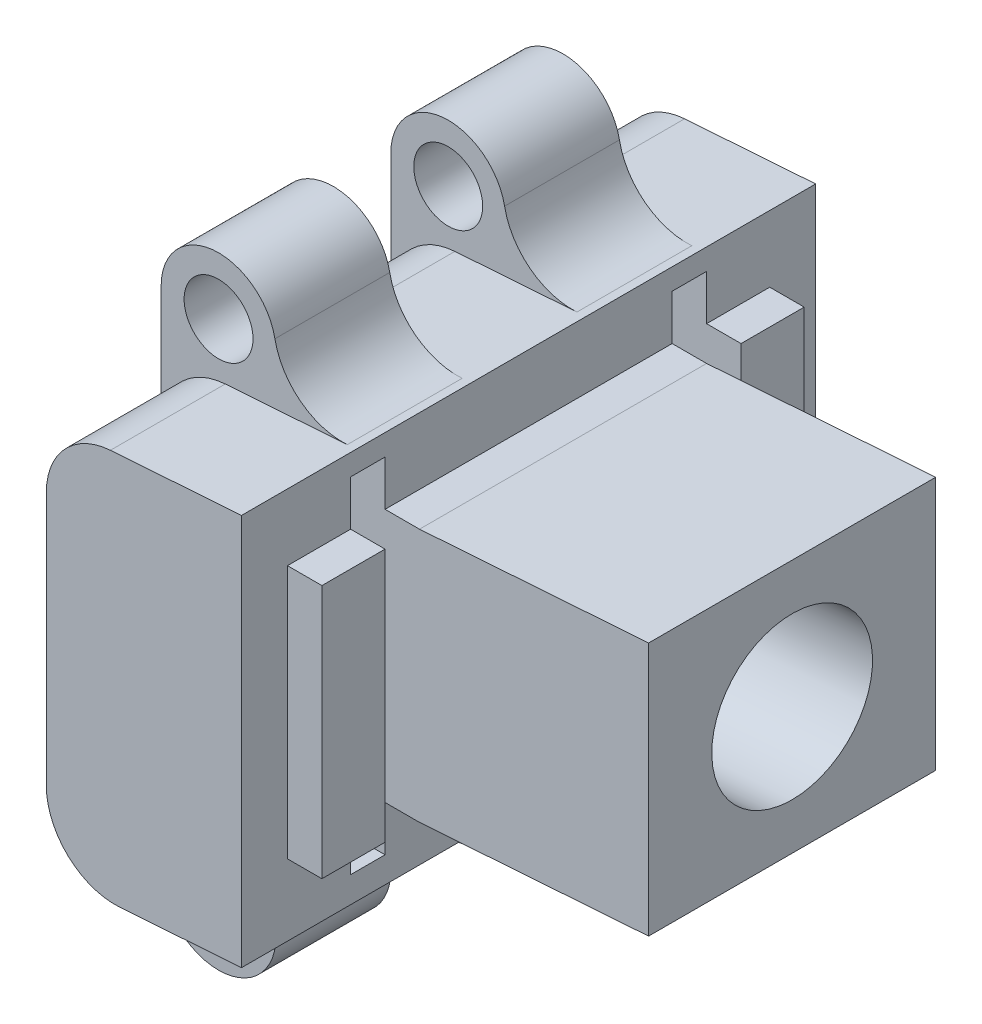
SolidWorks part; units mm, degrees
ref_plane "Front Plane" through (0, 0, 0) normal (0, 0, 1) x (1, 0, 0)
ref_plane "Top Plane" through (0, 0, 0) normal (0, 1, 0) x (1, 0, 0)
ref_plane "Right Plane" through (0, 0, 0) normal (1, 0, 0) x (0, 0, -1)
sketch "Sketch1" plane through (0, 0, 0) normal (1, 0, 0) x (0, 0, -1)
  line L1 (0, 0) -> (50, 0)
  line L2 (0, 0) -> (0, 34.11)
  line L3 (0, 34.11) -> (50, 34.11)
  line L4 (50, 0) -> (50, 34.11)
  dimension "D1" = 50
  dimension "D2" = 34.11
extrude "Boss-Extrude1" add sketch "Sketch1" along normal blind 20
sketch "Sketch2" plane through (0, 0, 0) normal (0, 0, 1) x (1, 0, 0)
  line L0 (3, 37.11) -> (3, 34.11) construction
  line L1 (20, 34.11) -> (0, 34.11) construction
  line L2 (0, 34.11) -> (0, 37.11)
  line L3 (0, 34.11) -> (3, 34.11)
  line L4 (3, 34.11) -> (6, 34.11)
  line L5 (6, 34.11) -> (6, 37.11)
  line L6 (6, 37.11) -> (3, 37.11) construction
  circle A0 centre (3, 37.11) radius 2
  arc A1 (6, 37.11) -> (0, 37.11) centre (3, 37.11) ccw
  dimension "D1" = 4
  dimension "D2" = 3
  dimension "D3" = 3
ref_plane "Plane1" through (0, 0, -10) normal (0, 0, 1) x (1, 0, 0)
sketch "Sketch3" plane through (0, 0, -10) normal (0, 0, 1) x (1, 0, 0)
  line L0 (5, 39.11) -> (5, 34.11) construction
  line L2 (0, 34.11) -> (0, 39.11)
  line L3 (0, 34.11) -> (5, 34.11)
  line L4 (5, 34.11) -> (10, 34.11)
  line L5 (10, 34.11) -> (10, 39.11)
  line L6 (10, 39.11) -> (5, 39.11) construction
  line L7 (0, 34.11) -> (0, 0) construction
  line L8 (20, 34.11) -> (0, 34.11) construction
  circle A0 centre (5, 39.11) radius 3
  arc A1 (10, 39.11) -> (0, 39.11) centre (5, 39.11) ccw
  dimension "D1" = 6
  dimension "D2" = 5
  dimension "D3" = 5
extrude "Boss-Extrude2" add sketch "Sketch3" against normal blind 10
pattern_linear "LPattern1" count 2 spacing 20 along (0, 0, -1) of "Boss-Extrude2"
ref_plane "Plane2" through (0, 17.055, 0) normal (0, 1, 0) x (1, 0, 0)
mirror "Mirror1" about plane through (0, 17.055, 0) normal (0, 1, 0) of "LPattern1", "Boss-Extrude2"
ref_plane "Plane3" through (0, 0, -25) normal (0, 0, 1) x (1, 0, 0)
sketch "Sketch4" plane through (0, 0, -25) normal (0, 0, 1) x (1, 0, 0)
  line L0 (20, 17.055) -> (0, 17.055) construction
  line L1 (20, 34.11) -> (20, 0) construction
  line L2 (0, 34.11) -> (0, 0) construction
  line L3 (10, 0) -> (10, 34.11) construction
  line L4 (20, 0) -> (0, 0) construction
  line L5 (20, 34.11) -> (0, 34.11) construction
  line L6 (10, 17.055) -> (20, 17.7543) construction
  dimension "D1" = 4
ref_plane "Plane4" through (20, 17.7543, -25) normal (0.9976, 0.0698, 0) x (0, 0, -1)
sketch "Sketch7" plane through (0, 0, 0) normal (0, 0, 1) x (1, 0, 0)
  line L0 (20, 34.11) -> (0, 34.11)
  line L1 (0, 34.11) -> (20, 35.5085)
  line L2 (20, 35.5085) -> (20, 34.11)
  dimension "D1" = 4
extrude "Boss-Extrude3" add sketch "Sketch7" against normal up to surface (50 mm away) up to face at (10, 17.055, -50)
sketch "Sketch8" plane through (0, 0, 0) normal (0, 0, 1) x (1, 0, 0)
  line L0 (0, 0) -> (20, 1.3985)
  line L1 (20, 35.5085) -> (20, 0) construction
  line L2 (20, 1.3985) -> (20, 0)
  line L3 (20, 0) -> (0, 0)
  dimension "D1" = 4
extrude "Cut-Extrude3" cut sketch "Sketch8" against normal blind 10
extrude "Cut-Extrude4" cut sketch "Sketch8<2>" against normal up to surface (30 mm away) from surface up to face at (5, -3.75, -30) starting at face at (5, -3.75, -20)
sketch "Sketch8<2>" plane through (0, 0, 0) normal (0, 0, 1) x (1, 0, 0) same geometry as "Sketch8"
extrude "Cut-Extrude5" cut sketch "Sketch8<3>" along direction (0, 0, 1) on the side against the normal up to surface (50 mm away) from surface up to face at (10, 17.4046, -50) starting at face at (5, -3.75, -40)
sketch "Sketch8<3>" plane through (0, 0, 0) normal (0, 0, 1) x (1, 0, 0) same geometry as "Sketch8"
sketch "Sketch9" plane through (0, 0, 0) normal (0, 0, 1) x (1, 0, 0)
  line L0 (20, 1.3985) -> (0, 0) construction
  line L1 (20, 0) -> (20, 1.3985) construction
  line L2 (10, 0) -> (20, 0) construction
  line L3 (20, 1.3985) -> (10, 0.6993)
  line L4 (20, 0) -> (20, 1.3985)
  line L5 (10, 0) -> (20, 0)
  line L6 (10, 0) -> (10, 0.6993)
extrude "Cut-Extrude6" cut sketch "Sketch9" against normal up to surface (50 mm away) up to face at (10, 17.7543, -50)
sketch "Sketch6" plane through (20, 0, 0) normal (1, 0, 0) x (0, 0, -1)
  line L0 (25, 35.5085) -> (25, 18.4535) construction
  line L3 (12.5, 18.4535) -> (37.5, 18.4535)
  line L4 (12.5, 3.4535) -> (12.5, 33.4535)
  line L5 (12.5, 33.4535) -> (9.5, 33.4535)
  line L6 (9.5, 33.4535) -> (9.5, 3.4535)
  line L7 (9.5, 3.4535) -> (12.5, 3.4535)
  line L8 (40.5, 33.4535) -> (40.5, 3.4535)
  line L9 (37.5, 33.4535) -> (40.5, 33.4535)
  line L10 (37.5, 3.4535) -> (37.5, 33.4535)
  line L11 (40.5, 3.4535) -> (37.5, 3.4535)
  line L12 (50, 35.5085) -> (0, 35.5085) construction
  line L13 (25, 18.4535) -> (25, 1.3985) construction
  line L14 (50, 1.3985) -> (0, 1.3985) construction
  point P9 (25, 18.4535)
  point P12 (12.5, 18.4535)
  dimension "D1" = 25
  dimension "D2" = 30
  dimension "D3" = 3
  dimension "D4" = 30
  dimension "D5" = 3
extrude "Cut-Extrude2" cut sketch "Sketch6" against normal blind 10 contours L6 L7 L4 L5 | L11 L8 L9 L10 region at (20, 18.4535, -39) region at (20, 18.4535, -11)
sketch "Sketch10" plane through (20, 0, 0) normal (1, 0, 0) x (0, 0, -1)
  line L0 (50, 35.5085) -> (0, 35.5085) construction
  line L1 (4, 29.5085) -> (46, 29.5085)
  line L2 (4, 29.5085) -> (4, 7.3985)
  line L3 (4, 7.3985) -> (46, 7.3985)
  line L4 (46, 29.5085) -> (46, 7.3985)
  line L5 (50, 1.3985) -> (50, 35.5085) construction
  line L6 (50, 1.3985) -> (0, 1.3985) construction
  line L7 (0, 35.5085) -> (0, 1.3985) construction
  line L9 (0, 35.5085) -> (50, 35.5085)
  line L10 (0, 35.5085) -> (0, 1.3985)
  line L11 (0, 1.3985) -> (50, 1.3985)
  line L12 (50, 35.5085) -> (50, 1.3985)
  dimension "D1" = 6
  dimension "D2" = 4
  dimension "D3" = 6
  dimension "D4" = 4
extrude "Cut-Extrude7" cut sketch "Sketch10" against normal blind 3
sketch "Sketch11" plane through (0, 1.3985, 0) normal (0, 1, 0) x (1, 0, 0)
  line L1 (20, 50) -> (17, 50)
  line L2 (20, 50) -> (20, 0)
  line L3 (20, 0) -> (17, 0)
  line L4 (17, 50) -> (17, 0)
extrude "Cut-Extrude8" cut sketch "Sketch11" against normal up to surface up to face at (6.6667, 0.4662, -25)
fillet "Fillet1" radius 6 10 edges at (10, 0.6993, -15) (10, 0.6993, -35) (10, 34.8093, -35) (10, 34.8093, -15) (0, 0, -5) (0, 0, -25) (0, 0, -45) (0, 34.11, -45) (0, 34.11, -25) (0, 34.11, -5)
sketch "Sketch5" plane through (20, 17.7543, -25) normal (0.9976, 0.0698, 0) x (0, 0, -1)
  line L1 (0, 17.711) -> (0, 0.6976) construction
  line L6 (25, 17.711) -> (-25, 17.711) construction
  line L10 (0, 0.6976) -> (0, -16.3159) construction
  line L11 (25, -16.3159) -> (-25, -16.3159) construction
  circle A0 centre (0, 0.6976) radius 7
  point P7 (0, 0.6976)
  dimension "D1" = 14
extrude "Cut-Extrude1" cut sketch "Sketch5" against normal blind 10 and the other way up to next
sketch "Sketch13" plane through (20, 0, 0) normal (1, 0, 0) x (0, 0, -1)
  line L0 (37.5, 3.4535) -> (37.5, 33.4535) construction
  line L1 (12.5, 7.3985) -> (37.5, 7.3985) construction
  line L2 (12.5, 3.4535) -> (12.5, 33.4535) construction
  line L3 (37.5, 29.5085) -> (12.5, 29.5085) construction
  line L4 (37.5, 7.3985) -> (37.5, 29.5085)
  line L5 (12.5, 7.3985) -> (37.5, 7.3985)
  line L6 (12.5, 7.3985) -> (12.5, 29.5085)
  line L7 (37.5, 29.5085) -> (12.5, 29.5085)
  ellipse E0 centre (25, 18.4535) end of major axis (25, 11.4364) minor radius 7 construction
  ellipse E1 centre (25, 18.4535) end of major axis (25, 11.4364) minor radius 7
extrude "Boss-Extrude4" add sketch "Sketch13" along direction (0.9976, 0.0698, 0) on the side of the normal blind 20
